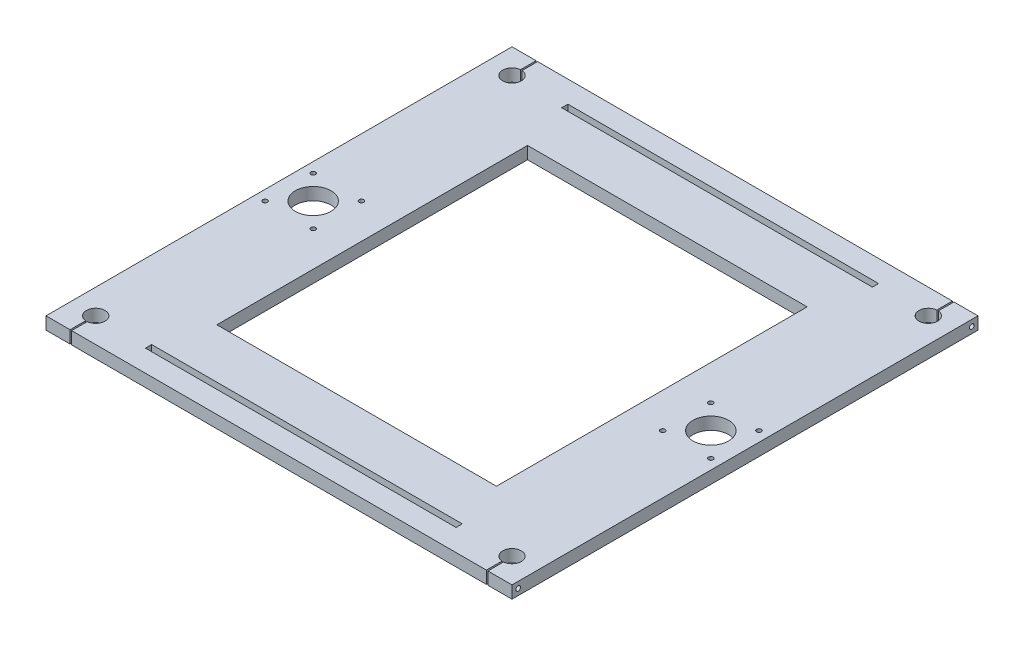
SolidWorks part; units mm, degrees
ref_plane "Front Plane" through (0, 0, 0) normal (0, 0, 1) x (1, 0, 0)
ref_plane "Top Plane" through (0, 0, 0) normal (0, 1, 0) x (1, 0, 0)
ref_plane "Right Plane" through (0, 0, 0) normal (1, 0, 0) x (0, 0, -1)
sketch "Sketch1" plane through (0, 0, 0) normal (0, 1, 0) x (1, 0, 0)
  line L0 (150, 150) -> (150, -150)
  line L1 (-150, -150) -> (150, -150)
  line L2 (-150, -150) -> (-150, 150)
  line L3 (-150, 150) -> (150, 150)
  line L5 (-150, -150) -> (150, 150) construction
  line L6 (-150, 150) -> (150, -150) construction
  line L7 (-90, -100) -> (90, -100)
  line L8 (-90, -100) -> (-90, 100)
  line L9 (-90, 100) -> (90, 100)
  line L10 (90, -100) -> (90, 100)
  line L11 (-90, -100) -> (90, 100) construction
  line L12 (-90, 100) -> (90, -100) construction
  point P0 (0, 0)
  point P13 (0, 0)
  dimension "D4" = 300
  dimension "D1" = 300
  dimension "D2" = 180
  dimension "D3" = 200
extrude "Boss-Extrude1" add sketch "Sketch1" along normal blind 8
sketch "Sketch2" plane through (0, 0, 0) normal (0, 1, 0) x (1, 0, 0)
  line L0 (150, 150) -> (-150, 150) construction
  line L1 (150, 150) -> (-150, 150) construction
  line L2 (150, -150) -> (150, 150) construction
  line L3 (133.5, 150) -> (134.5, 150)
  line L4 (133.5, 150) -> (133.5, 139.9791)
  line L5 (134, 134) -> (134, 150) construction
  line L6 (134.5, 150) -> (134.5, 139.9791)
  arc A0 (133.5, 139.9791) -> (134.5, 139.9791) centre (134, 134) ccw
  point P6 (131.0158, 128.7948)
  dimension "D1" = 12
  dimension "D2" = 16
  dimension "D3" = 16
  dimension "D4" = 1
extrude "Cut-Extrude1" cut sketch "Sketch2" along normal through all
sketch "Sketch3" plane through (150, 0, 0) normal (1, 0, 0) x (0, 0, -1)
  line L0 (146, 4) -> (150, 4) construction
  line L2 (150, 8) -> (150, 0) construction
  circle A0 centre (146, 4) radius 1.5
  dimension "D1" = 3
  dimension "D2" = 4
extrude "Cut-Extrude2" cut sketch "Sketch3" against normal up to surface (16.5 mm away) up to face at (133.5, 4, -144.9896)
mirror "Mirror3" about plane through (0, 0, 0) normal (0, 0, 1) of "Cut-Extrude2", "Cut-Extrude1"
mirror "Mirror4" about plane through (0, 0, 0) normal (1, 0, 0) of "Cut-Extrude2", "Cut-Extrude1", "Mirror3"
sketch "Sketch5" plane through (0, 0, 0) normal (0, 1, 0) x (1, 0, 0)
  line L0 (-1134, 134) -> (48866, 134) construction
  line L2 (-100, 136) -> (100, 136)
  line L3 (-100, 136) -> (-100, 132)
  line L4 (-100, 132) -> (100, 132)
  line L5 (100, 136) -> (100, 132)
  line L6 (-100, 136) -> (100, 132) construction
  line L7 (-100, 132) -> (100, 136) construction
  point P1 (0, 134)
  dimension "D1" = 4
  dimension "D2" = 200
extrude "Cut-Extrude5" cut sketch "Sketch5" along normal through all
mirror "Mirror5" about plane through (0, 0, 0) normal (0, 0, 1) of "Cut-Extrude5"
sketch "Sketch6" plane through (0, 0, 0) normal (0, 1, 0) x (1, 0, 0)
  line L0 (-134, -866) -> (-134, 49134) construction
  line L2 (-143.5, -15.5) -> (-112.5, -15.5) construction
  line L3 (-143.5, -15.5) -> (-143.5, 15.5) construction
  line L4 (-143.5, 15.5) -> (-112.5, 15.5) construction
  line L5 (-112.5, -15.5) -> (-112.5, 15.5) construction
  line L6 (-143.5, -15.5) -> (-112.5, 15.5) construction
  line L7 (-143.5, 15.5) -> (-112.5, -15.5) construction
  circle A0 centre (-128, 0) radius 11.5
  circle A1 centre (-112.5, 15.5) radius 1.5
  circle A2 centre (-112.5, -15.5) radius 1.5
  circle A3 centre (-143.5, 15.5) radius 1.5
  circle A4 centre (-143.5, -15.5) radius 1.5
  dimension "D1" = 23
  dimension "D5" = 3
  dimension "D6" = 3
  dimension "D7" = 3
  dimension "D8" = 3
  dimension "D2" = 6
  dimension "D3" = 31
  dimension "D4" = 31
extrude "Cut-Extrude6" cut sketch "Sketch6" along normal through all
mirror "Mirror6" about plane through (0, 0, 0) normal (1, 0, 0) of "Cut-Extrude6"
